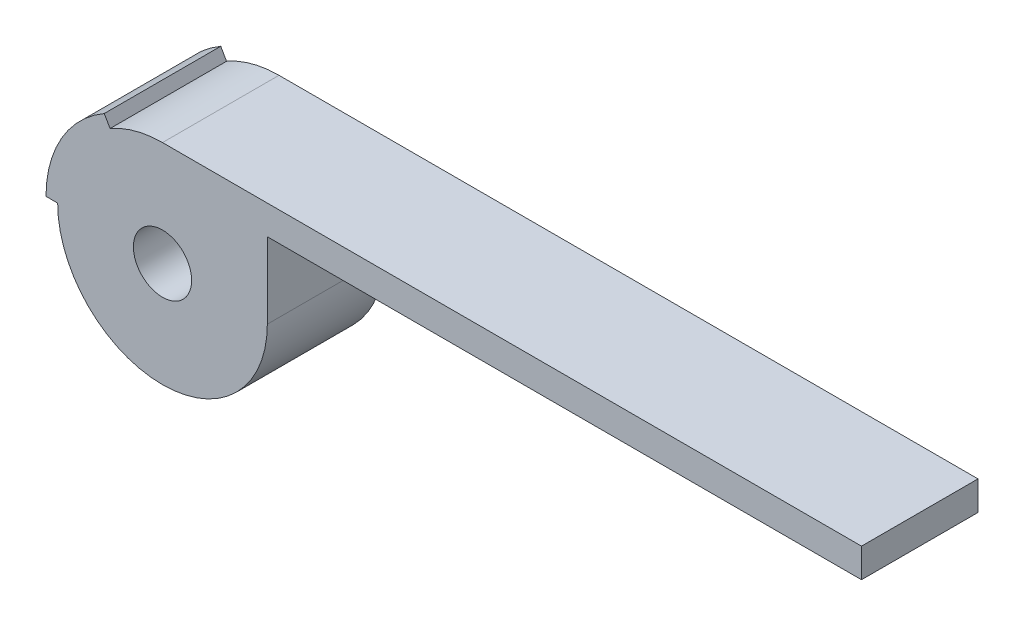
SolidWorks part; units mm, degrees
ref_plane "Front Plane" through (0, 0, 0) normal (0, 0, 1) x (1, 0, 0)
ref_plane "Top Plane" through (0, 0, 0) normal (0, 1, 0) x (1, 0, 0)
ref_plane "Right Plane" through (0, 0, 0) normal (1, 0, 0) x (0, 0, -1)
sketch "Sketch1" plane through (0, 0, 0) normal (0, 0, 1) x (1, 0, 0)
  line L0 (0, 11.43) -> (76.2, 11.43)
  line L1 (76.2, 11.43) -> (76.2, 8.255)
  line L2 (76.2, 8.255) -> (11.43, 8.255)
  line L3 (11.43, 8.255) -> (11.43, 0)
  line L4 (0, 0) -> (-11.43, 0) construction
  line L5 (-11.43, 0) -> (-12.7, 0)
  line L7 (0, 0) -> (-5.715, 9.8987) construction
  line L8 (-5.715, 9.8987) -> (-6.35, 10.9985)
  circle A0 centre (0, 0) radius 11.43
  circle A1 centre (0, 0) radius 3.175
  arc A2 (-12.7, 0) -> (-6.35, 10.9985) centre (0, 0) cw
  circle A3 centre (0, 0) radius 12.7 construction
  dimension "D1" = 6.35
  dimension "D2" = 25.4
  dimension "D5" = 60
  dimension "D3" = 76.2
  dimension "D4" = 3.175
  dimension "D6" = 1.27
extrude "Boss-Extrude1" add sketch "Sketch1" along normal blind 12.7 contours A0 A1 | A0 L3 L2 L1 L0 | A2 L5 A0 L8 region at (39.6232, 9.7266, 0) region at (7.8536, 7.8536, 0) region at (-9.9869, 5.7659, 0)
